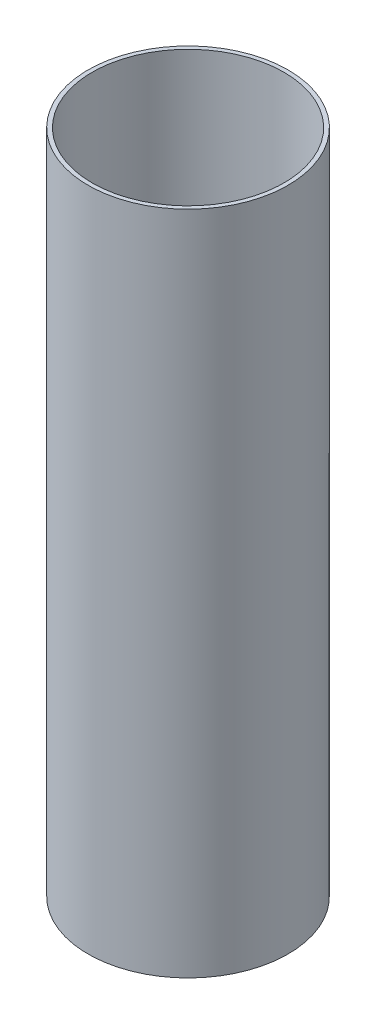
SolidWorks part; units mm, degrees
material "Hexcel AS4C (3000 Filaments)"
ref_plane "Front Plane" through (0, 0, 0) normal (0, 0, 1) x (1, 0, 0)
ref_plane "Top Plane" through (0, 0, 0) normal (0, 1, 0) x (1, 0, 0)
ref_plane "Right Plane" through (0, 0, 0) normal (1, 0, 0) x (0, 0, -1)
sketch "Sketch2" plane through (0, 0, 0) normal (0, 0, 1) x (1, 0, 0)
  line L0 (0, 0) -> (0, 51.225) construction
  line L1 (26.9875, -11.2955) -> (28.1305, -11.2955)
  line L2 (26.9875, -11.2955) -> (26.9875, -198.6205)
  line L3 (26.9875, -198.6205) -> (28.1305, -198.6205)
  line L4 (28.1305, -11.2955) -> (28.1305, -198.6205)
revolve "Revolve1" add sketch "Sketch2" angle 360 about L0
